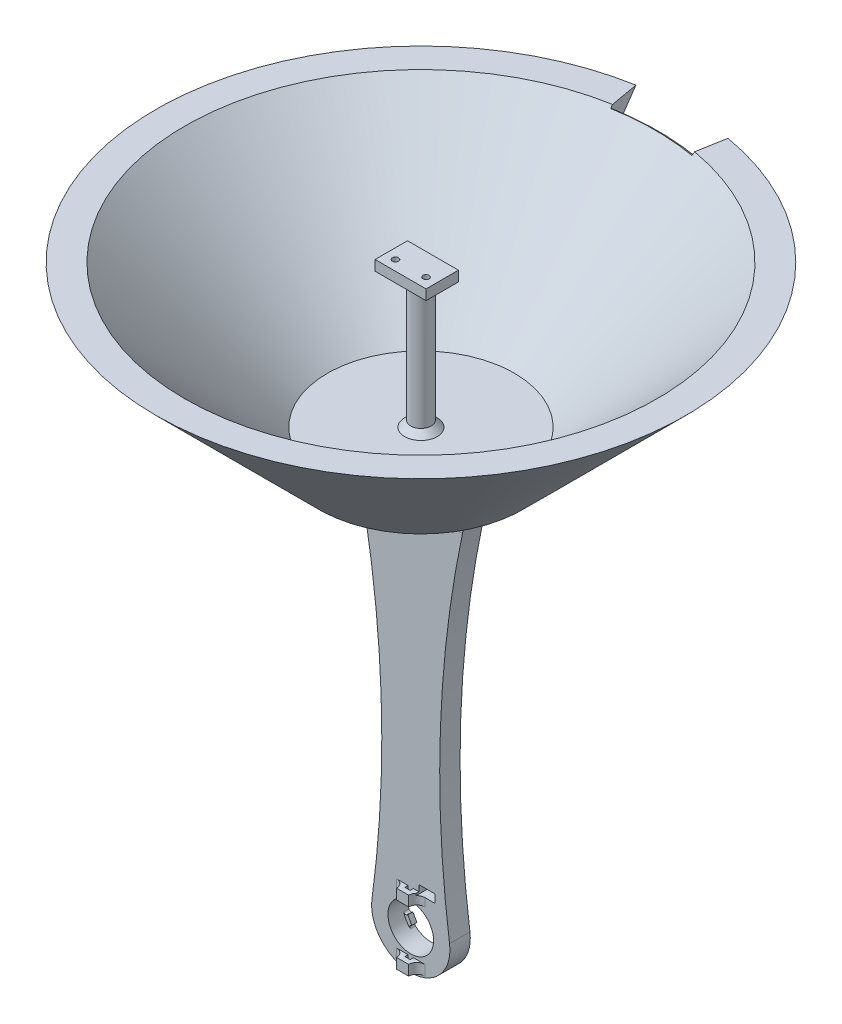
SolidWorks part; units mm, degrees
ref_plane "Front Plane" through (0, 0, 0) normal (0, 0, 1) x (1, 0, 0)
ref_plane "Top Plane" through (0, 0, 0) normal (0, 1, 0) x (1, 0, 0)
ref_plane "Right Plane" through (0, 0, 0) normal (1, 0, 0) x (0, 0, -1)
sketch "Sketch1" plane through (0, 0, 0) normal (0, 0, 1) x (1, 0, 0)
  line L0 (0, 0) -> (0, 200) construction
  line L1 (-15, 101.836) -> (15, 101.836) construction
  line L2 (-30, 200) -> (30, 200)
  circle A0 centre (0, 0) radius 11.2
  circle A1 centre (0, 0) radius 19.2
  arc A2 (-19.0212, 2.6141) -> (-30, 200) centre (-531.8309, 73.0894) ccw
  arc A3 (19.0212, 2.6141) -> (30, 200) centre (531.8309, 73.0894) cw
  point P10 (-15, 101.836)
  point P12 (15, 101.836)
  dimension "D1" = 22.4
  dimension "D2" = 8
  dimension "60" = 60
  dimension "D4" = 30
  dimension "D5" = 200
extrude "Boss-Extrude1" add sketch "Sketch1" along normal blind 10 contours A1 A3 L2 A2 | A1 A0 region at (0, 118.4726, 0) region at (0, 18.6569, 0)
sketch "Sketch2" plane through (0, 0, 0) normal (0, 0, -1) x (-1, 0, 0)
  line L0 (0, 11.2) -> (0, 0) construction
  line L6 (-2, 13.2) -> (2, 13.2)
  line L7 (-2, 13.2) -> (-2, 9.2)
  line L8 (-2, 9.2) -> (2, 9.2)
  line L9 (2, 13.2) -> (2, 9.2)
  line L10 (-2, 13.2) -> (2, 9.2) construction
  line L11 (-2, 9.2) -> (2, 13.2) construction
  circle A0 centre (0, 0) radius 11.2 construction
  point P0 (0, 11.2)
  dimension "D1" = 4
  dimension "D2" = 4
ref_axis "Axis1" through (0, 0, 10) along (0, 0, -1)
sketch "Sketch3" plane through (0, 0, 10) normal (0, 0, 1) x (1, 0, 0)
  line L0 (0, 0) -> (0, 22.4)
  line L1 (-5.9851, 0) -> (43.2633, 0) construction
  line L2 (-3, 17.2) -> (3, 17.2)
  line L3 (-3, 17.2) -> (-3, 12.2)
  line L4 (-3, 12.2) -> (3, 12.2)
  line L5 (3, 17.2) -> (3, 12.2)
  line L6 (-3, 17.2) -> (3, 12.2) construction
  line L7 (-3, 12.2) -> (3, 17.2) construction
  line L8 (-3, -12.2) -> (3, -12.2)
  line L9 (3, -17.2) -> (3, -12.2)
  line L10 (-3, -17.2) -> (3, -17.2)
  line L11 (-3, -17.2) -> (-3, -12.2)
  line L12 (0, 11.2) -> (7.4681, 11.2) construction
  circle A1 centre (0, 0) radius 11.2 construction
  point P2 (0, 14.7)
  dimension "D1" = 5
  dimension "D2" = 6
  dimension "D3" = 1
extrude "Boss-Extrude3" add sketch "Sketch3" along normal blind 4 contours L5 L2 L0 L4 | L3 L4 L0 L2 | L11 L10 L9 L8 region at (-1.5, 14.7, 10) region at (1.5, 14.7, 10) region at (0, -14.7, 10)
fillet "Fillet6" radius 4 4 edges at (-3, -14.7, 10) (3, -14.7, 10) (3, 14.7, 10) (-3, 14.7, 10)
sketch "Sketch5" plane through (0, 17.2, 0) normal (0, 1, 0) x (1, 0, 0)
  line L0 (-30, -10) -> (30, -10) construction
  line L1 (-1.3, -10) -> (1.3, -10)
  line L2 (-1.3, -10) -> (-1.3, -11.6)
  line L3 (-1.3, -11.6) -> (1.3, -11.6)
  line L4 (1.3, -10) -> (1.3, -11.6)
  point P6 (0, -10)
  dimension "D1" = 1.6
  dimension "D2" = 2.6
extrude "Cut-Extrude1" cut sketch "Sketch5" against normal through all both
sketch "Sketch6" plane through (0, 0, 0) normal (1, 0, 0) x (0, 0, -1)
  line L0 (-5, 200) -> (45, 200)
  line L1 (45, 200) -> (125, 280)
  line L2 (125, 280) -> (-5, 280)
  line L3 (-5, 200) -> (-5, 280)
  line L4 (-10, 200) -> (0, 200) construction
  line L5 (40.8579, 210) -> (100.8579, 270)
  line L6 (100.8579, 270) -> (5, 270)
  line L7 (5, 210) -> (5, 270)
  line L8 (5, 210) -> (40.8579, 210)
  line L9 (5, 210) -> (-5, 210)
  line L10 (100.8579, 270) -> (110.8579, 280)
  point P4 (-5, 200)
  dimension "D1" = 50
  dimension "D2" = 130
  dimension "D3" = 45
  dimension "D4" = 10
revolve "Revolve1" add sketch "Sketch6" angle 360 about L3 region at (0, 205, 3.4736)
fillet "Fillet7" radius 20 2 edges at (0, 200, 0) (0, 200, 10)
sketch "Sketch7" plane through (0, 210, 0) normal (0, 1, 0) x (1, 0, 0)
  circle A0 centre (0, -5) radius 45.8579 construction
  circle A1 centre (0, -5) radius 45.8579
  circle A2 centre (0, -5) radius 5
  dimension "D1" = 10
extrude "Boss-Extrude4" add sketch "Sketch7" along normal blind 65 separate body contours A2 region at (0, 210, 5)
sketch "Sketch8" plane through (0, 275, 0) normal (0, 1, 0) x (1, 0, 0)
  line L1 (-12.5, -15) -> (12.5, -15)
  line L2 (-12.5, -15) -> (-12.5, 5)
  line L3 (-12.5, 5) -> (12.5, 5)
  line L4 (12.5, -15) -> (12.5, 5)
  line L5 (-12.5, -15) -> (12.5, 5) construction
  line L6 (-12.5, 5) -> (12.5, -15) construction
  circle A1 centre (0, -5) radius 5
  circle A2 centre (0, -5) radius 5
  circle M4 centre (0, -5) radius 5
  dimension "D2" = 20
  dimension "D3" = 25
  dimension "D1" = 0
extrude "Boss-Extrude5" add sketch "Sketch8" along normal blind 5 contours L1 L4 L3 M4 | M4 | L3 L2 L1 M4 region at (-12.1798, 275, 5) region at (0, 275, 5)
sketch "Sketch10" plane through (0, 280, 0) normal (0, 1, 0) x (1, 0, 0)
  line L0 (0, -15) -> (0, 14.608) construction
  line L1 (-12.5, -15) -> (12.5, -15) construction
  line L2 (0, -10) -> (0, 0) construction
  line L3 (-7.5, -10) -> (-7.5, -8.5) construction
  line L4 (-7.5, -10) -> (-9, -10) construction
  line L6 (-12.5, -15) -> (-12.5, 5) construction
  circle A0 centre (-7.5, -10) radius 1.5
  circle A1 centre (7.5, -10) radius 1.5
  point P17 (-12.5, -5)
  dimension "D1" = 3
  dimension "D2" = 7.5
  dimension "D3" = 5
  dimension "D4" = 15
  dimension "D5" = 5
  dimension "D6" = 7.5
extrude "Cut-Extrude2" cut sketch "Sketch10" against normal up to next (5 mm away)
fillet "Fillet8" radius 1 1 edges at (0, 275, 10)
ref_plane "Plane1" through (0, 0, 5) normal (0, 0, 1) x (1, 0, 0)
sketch "Sketch12" plane through (0, 0, 5) normal (0, 0, 1) x (1, 0, 0)
  line L0 (5, 213) -> (8, 210)
  line L1 (5, 210) -> (5, 274) construction
  line L2 (45.8579, 210) -> (-45.8579, 210) construction
  line L3 (8, 210) -> (5, 210)
  line L4 (5, 210) -> (5, 213)
  line L5 (0, 210) -> (0, 266.2577)
  dimension "D1" = 3
  dimension "D2" = 3
revolve "Revolve2" add sketch "Sketch12" angle 360 about L5 region at (6, 211, 5)
extrude "Boss-Extrude6" add sketch "Sketch2" against normal blind 2.5
pattern_circular "CirPattern1" count 3 over 360 about axis through (0, 0, 10) along (0, 0, -1) of "Boss-Extrude6"
fillet "Fillet9" radius 1 6 edges at (2, 11.02, 1.25) (-2, 11.02, 1.25) (8.5436, -7.242, 1.25) (10.5436, -3.7779, 1.25) (-8.5436, -7.242, 1.25) (-10.5436, -3.7779, 1.25)
ref_axis "Axis3" through (0, 274, 5) along (0, -1, 0)
sketch "Sketch13" plane through (0, 0, 0) normal (1, 0, 0) x (0, 0, -1)
  line L0 (45, 200) -> (125, 280) construction
  line L1 (125, 280) -> (-135, 280) construction
  line L2 (45, 200) -> (111.3431, 266.3431)
  line L3 (105.6863, 280) -> (-135, 280)
  line L4 (105.6863, 280) -> (125, 280)
  line L5 (125, 280) -> (111.3431, 266.3431)
  arc A0 (111.3431, 266.3431) -> (105.6863, 280) centre (105.6863, 272) ccw
  dimension "D1" = 8
revolve "Cut-Revolve1" cut sketch "Sketch13" angle 20 mid plane about axis through (0, 274, 5) along (0, -1, 0) region at (0, 276.4455, -116.4186)
sketch "Sketch14" plane through (0, 280, 0) normal (0, 1, 0) x (1, 0, 0)
  line L0 (-9.4113, -12.5) -> (10.1269, -12.5)
  line L1 (7.5, -10) -> (7.5, -11.5)
  line L2 (-12.5, 0.9) -> (12.5, 0.9)
  line L3 (12.5, -15) -> (12.5, 5) construction
  line L4 (-12.5, -15) -> (-12.5, 5) construction
  line L6 (-12.5, 5) -> (12.5, 5)
  line L7 (-12.5, 5) -> (-12.5, 0.9)
  line L8 (-12.5, 0.9) -> (12.5, 0.9)
  line L9 (12.5, 5) -> (12.5, 0.9)
  circle A0 centre (7.5, -10) radius 1.5 construction
  point P2 (7.5, -11.5)
  line M10 (12.5, -15) -> (12.5, 5)
  line M11 (12.5, 5) -> (-12.5, 5)
  line M12 (-12.5, 5) -> (-12.5, -15)
  dimension "D1" = 1
  dimension "D2" = 13.4
extrude "Cut-Extrude3" cut sketch "Sketch14" against normal up to next contours L2 M12 M10 M11 region at (0, 280, -2.95)
sketch "Sketch15" plane through (0, 0, 0) normal (0, 0, -1) x (-1, 0, 0)
  line L0 (-12, 16.2) -> (-4, 16.2) construction
  line L1 (-12, 20.2) -> (-4, 20.2)
  line L2 (-12, 20.2) -> (-12, 16.2)
  line L3 (-12, 16.2) -> (-4, 16.2)
  line L4 (-4, 20.2) -> (-4, 16.2)
  point P6 (0, 0)
  point P7 (-4.5174, 16.2)
  point P10 (-3, 16.2)
extrude "Cut-Extrude6" cut sketch "Sketch15" against normal blind 20
